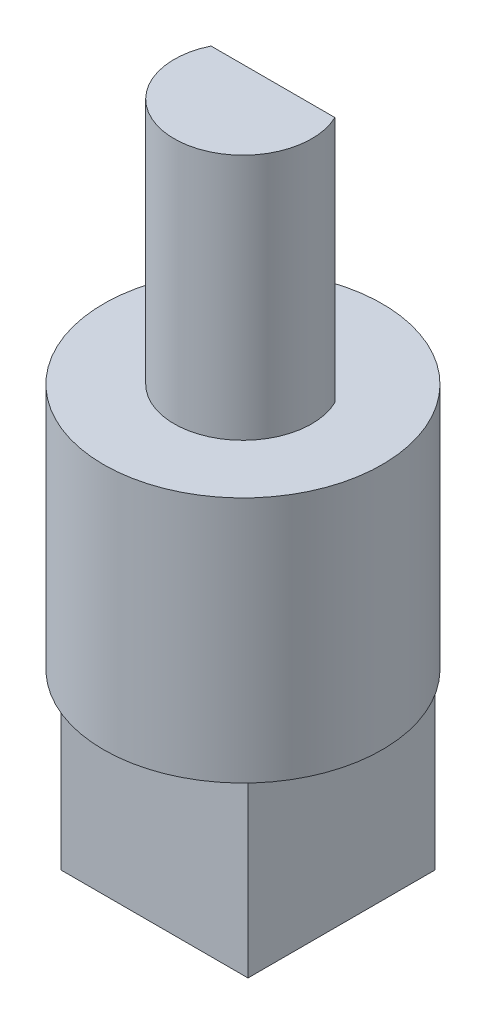
SolidWorks part; units mm, degrees
ref_plane "Front Plane" through (0, 0, 0) normal (0, 0, 1) x (1, 0, 0)
ref_plane "Top Plane" through (0, 0, 0) normal (0, 1, 0) x (1, 0, 0)
ref_plane "Right Plane" through (0, 0, 0) normal (1, 0, 0) x (0, 0, -1)
sketch "Sketch1" plane through (0, 0, 0) normal (0, 1, 0) x (1, 0, 0)
  line L7 (2.65, -2.5069) -> (-2.65, -2.5069)
  line L8 (2.65, -2.5069) -> (2.65, 2.7931)
  line L9 (2.65, 2.7931) -> (-2.65, 2.7931)
  line L10 (-2.65, -2.5069) -> (-2.65, 2.7931)
  line L11 (2.65, -2.5069) -> (-2.65, 2.7931) construction
  line L12 (2.65, 2.7931) -> (-2.65, -2.5069) construction
  point P0 (0, 0)
  point P3 (10.3027, -3.8772)
  point P6 (0, 0)
  point P7 (6.9838, -1.7)
  dimension "D1" = 5.3
  dimension "D4" = 90
extrude "Boss-Extrude1" add sketch "Sketch1" along normal blind 5
sketch "Sketch2" plane through (0, 5, 0) normal (0, 1, 0) x (1, 0, 0)
  circle A1 centre (0, 0) radius 3.95
  dimension "D1" = 7.9
extrude "Boss-Extrude2" add sketch "Sketch2" along normal blind 7
sketch "Sketch3" plane through (0, 12, 0) normal (0, 1, 0) x (1, 0, 0)
  circle A0 centre (0, 0) radius 1.95
  dimension "D1" = 3.9
extrude "Boss-Extrude3" add sketch "Sketch3" along normal blind 7
sketch "Sketch4" plane through (0, 19, 0) normal (0, 1, 0) x (1, 0, 0)
  line L0 (0, -1.95) -> (0, 0.85) construction
  line L1 (0, 0.85) -> (1.755, 0.85) construction
  line L2 (0, 0.85) -> (-1.755, 0.85) construction
  line L3 (-1.755, 0.85) -> (1.755, 0.85)
  circle A0 centre (0, 0) radius 1.95 construction
  circle A1 centre (0, 0) radius 1.95 construction
  arc A2 (-1.755, 0.85) -> (1.755, 0.85) centre (0, 0) cw
  dimension "D1" = 2.8
extrude "Cut-Extrude1" cut sketch "Sketch4" against normal blind 7
